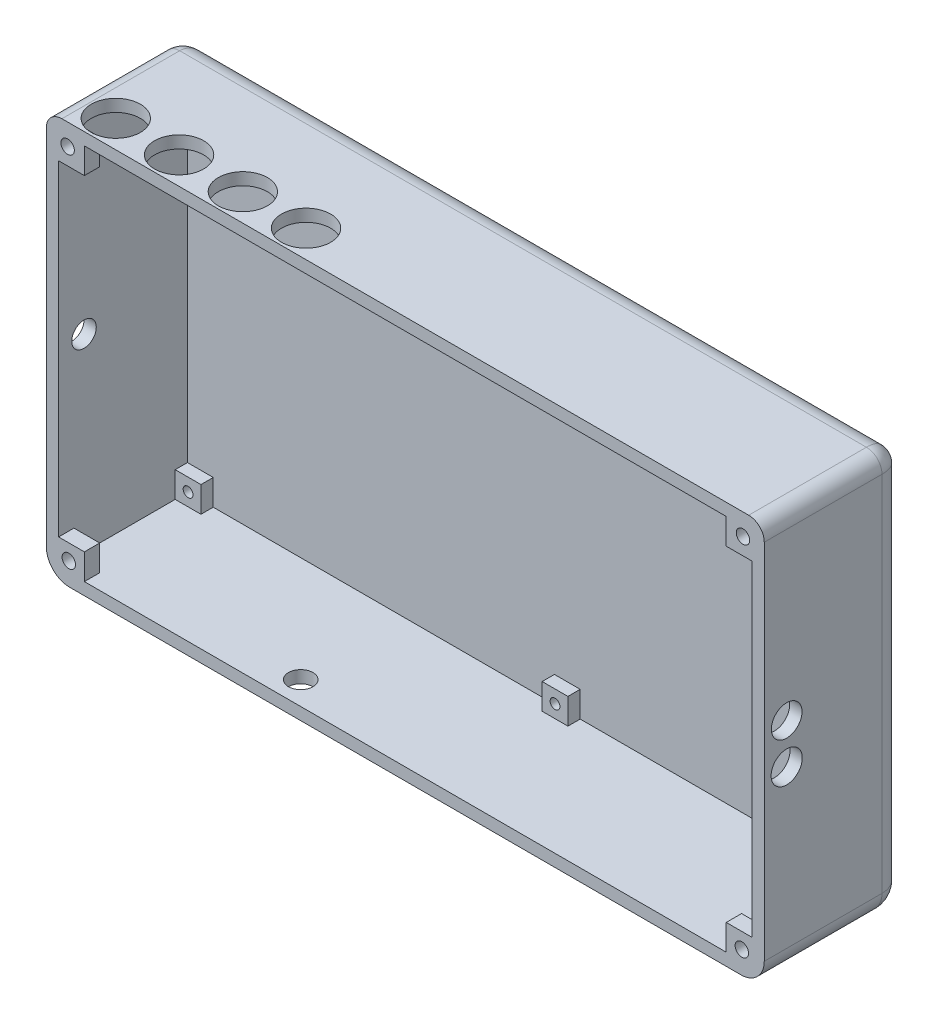
SolidWorks part; units mm, degrees
ref_plane "Front Plane" through (0, 0, 0) normal (0, 0, 1) x (1, 0, 0)
ref_plane "Top Plane" through (0, 0, 0) normal (0, 1, 0) x (1, 0, 0)
ref_plane "Right Plane" through (0, 0, 0) normal (1, 0, 0) x (0, 0, -1)
sketch "Sketch1" plane through (0, 0, 0) normal (0, 0, 1) x (1, 0, 0)
  line L1 (58.5, -32.75) -> (-58.5, -32.75)
  line L2 (58.5, -32.75) -> (58.5, 32.75)
  line L3 (58.5, 32.75) -> (-58.5, 32.75)
  line L4 (-58.5, -32.75) -> (-58.5, 32.75)
  line L5 (0, 32.75) -> (0, -32.75) construction
  line L6 (58.5, 0) -> (-58.5, 0) construction
  point P0 (0, 0)
  dimension "D1" = 117
  dimension "D2" = 65.5
extrude "Boss-Extrude1" add sketch "Sketch1" along normal blind 23
sketch "Sketch2" plane through (0, 0, 23) normal (0, 0, 1) x (1, 0, 0)
  line L1 (56.5, -30.75) -> (-56.5, -30.75)
  line L2 (56.5, -30.75) -> (56.5, 30.75)
  line L3 (56.5, 30.75) -> (-56.5, 30.75)
  line L4 (-56.5, -30.75) -> (-56.5, 30.75)
  line L5 (0, 30.75) -> (0, -30.75) construction
  line L6 (56.5, 0) -> (-56.5, 0) construction
  point P1 (0, 0)
  dimension "D1" = 113
  dimension "D2" = 61.5
extrude "Cut-Extrude1" cut sketch "Sketch2" against normal blind 21
sketch "Sketch3" plane through (0, 0, 2) normal (0, 0, 1) x (1, 0, 0)
  line L1 (-56.5, 30.75) -> (-52.3, 30.75)
  line L2 (-56.5, 30.75) -> (-56.5, 26.55)
  line L3 (-56.5, 26.55) -> (-52.3, 26.55)
  line L4 (-52.3, 30.75) -> (-52.3, 26.55)
  dimension "D1" = 4.2
  dimension "D2" = 4.2
extrude "Boss-Extrude3" add sketch "Sketch3" along normal blind 2
sketch "Sketch5" plane through (0, 0, 2) normal (0, 0, 1) x (1, 0, 0)
  line L0 (-56.5, -30.75) -> (7.5, -30.75) construction
  line L1 (-56.5, -30.75) -> (56.5, -30.75) construction
  line L3 (-56.5, -30.75) -> (-52.3, -30.75)
  line L4 (-56.5, -30.75) -> (-56.5, -26.55)
  line L5 (-56.5, -26.55) -> (-52.3, -26.55)
  line L6 (-52.3, -30.75) -> (-52.3, -26.55)
  line L7 (7.5, -30.75) -> (3.3, -30.75)
  line L8 (7.5, -30.75) -> (7.5, -26.55)
  line L9 (7.5, -26.55) -> (3.3, -26.55)
  line L10 (3.3, -30.75) -> (3.3, -26.55)
  dimension "D1" = 64
  dimension "D2" = 4.2
  dimension "D3" = 4.2
  dimension "D4" = 4.2
  dimension "D5" = 4.2
extrude "Boss-Extrude4" add sketch "Sketch5" along normal blind 2
sketch "Sketch6" plane through (0, 0, 2) normal (0, 0, 1) x (1, 0, 0)
  line L0 (-56.5, 26.55) -> (7.5, 26.55) construction
  line L1 (7.5, -26.55) -> (7.5, 30.75) construction
  line L5 (7.5, 30.75) -> (3.3, 30.75)
  line L6 (7.5, 30.75) -> (7.5, 26.55)
  line L7 (7.5, 26.55) -> (3.3, 26.55)
  line L8 (3.3, 30.75) -> (3.3, 26.55)
  dimension "D1" = 64
  dimension "D2" = 4.2
  dimension "D3" = 4.2
extrude "Boss-Extrude5" add sketch "Sketch6" along normal blind 2
sketch "Sketch7" plane through (0, 0, 4) normal (0, 0, 1) x (1, 0, 0)
  line L0 (-56.5, 30.75) -> (-52.3, 26.55) construction
  line L1 (-52.3, 26.55) -> (-52.3, 30.75) construction
  line L2 (-52.3, 26.55) -> (-52.3, 30.75) construction
  line L3 (-52.3, 30.75) -> (-56.5, 26.55) construction
  line L4 (-56.5, 26.55) -> (7.5, 30.75) construction
  line L5 (7.5, 30.75) -> (3.3, 26.55) construction
  line L6 (3.3, 26.55) -> (7.5, 26.55) construction
  line L7 (7.5, 26.55) -> (3.3, 30.75) construction
  line L8 (3.3, 30.75) -> (7.5, -30.75) construction
  line L9 (7.5, -30.75) -> (3.3, -26.55) construction
  line L10 (7.5, -26.55) -> (3.3, -26.55) construction
  line L11 (3.3, -26.55) -> (7.5, -26.55) construction
  line L12 (7.5, -26.55) -> (3.3, -30.75) construction
  line L13 (3.3, -30.75) -> (-56.5, -30.75) construction
  line L14 (-56.5, -30.75) -> (-52.3, -26.55) construction
  line L15 (-52.3, -26.55) -> (-52.3, -30.75) construction
  line L16 (-52.3, -30.75) -> (-56.5, -26.55) construction
  circle A0 centre (-54.4, -28.65) radius 0.8
  dimension "D1" = 1.6
extrude "Cut-Extrude2" cut sketch "Sketch7" against normal blind 2
sketch "Sketch8" plane through (0, 0, 4) normal (0, 0, 1) x (1, 0, 0)
  line L0 (3.3, -26.55) -> (3.6877, -26.9377) construction
  line L1 (7.5, -30.75) -> (3.3, -26.55) construction
  line L2 (3.3, -26.55) -> (7.5, -26.55) construction
  line L3 (7.5, -26.55) -> (3.3, -30.75) construction
  circle A0 centre (5.4, -28.65) radius 0.8
  dimension "D1" = 1.6
extrude "Cut-Extrude3" cut sketch "Sketch8" against normal blind 2
sketch "Sketch9" plane through (0, 0, 4) normal (0, 0, 1) x (1, 0, 0)
  line L0 (3.3, 30.75) -> (7.5, 26.55) construction
  line L1 (7.5, 26.55) -> (7.5, 30.75) construction
  line L2 (7.5, 30.75) -> (3.3, 26.55) construction
  circle A0 centre (5.4, 28.65) radius 0.8
  dimension "D1" = 1.6
extrude "Cut-Extrude4" cut sketch "Sketch9" against normal blind 2
sketch "Sketch10" plane through (0, 0, 4) normal (0, 0, 1) x (1, 0, 0)
  line L0 (-56.5, 30.75) -> (-52.3, 26.55) construction
  line L1 (-52.3, 26.55) -> (-52.3, 30.75) construction
  line L2 (-52.3, 30.75) -> (-56.5, 26.55) construction
  circle A0 centre (-54.4, 28.65) radius 0.8
  dimension "D1" = 1.6
extrude "Cut-Extrude6" cut sketch "Sketch10" against normal blind 2
sketch "Sketch11" plane through (0, 30.75, 0) normal (0, -1, 0) x (-1, 0, 0)
  line L0 (56.5, -23) -> (56.5, -14.11) construction
  line L1 (56.5, -4) -> (56.5, -23) construction
  line L4 (47.6269, -18.555) -> (41.3092, -18.555) construction
  line L5 (37.3092, -18.555) -> (30.9182, -18.555) construction
  line L6 (26.9182, -18.555) -> (20.6182, -18.555) construction
  circle A0 centre (51.6269, -18.555) radius 4
  circle A1 centre (41.3092, -18.555) radius 4
  circle A2 centre (30.9182, -18.555) radius 4
  circle A3 centre (20.6182, -18.555) radius 4
  point P10 (56.5, -18.555)
  dimension "D2" = 8
  dimension "D3" = 8
  dimension "D4" = 8
  dimension "D5" = 8
  dimension "D1" = 8.89
extrude "Cut-Extrude7" cut sketch "Sketch11" against normal through all
sketch "Sketch12" plane through (-56.5, 0, 0) normal (1, 0, 0) x (0, 0, -1)
  line L0 (-23, 30.75) -> (-23, -30.75) construction
  line L1 (-23, -30.75) -> (-23, 0) construction
  line L2 (-23, 0) -> (-2, 0) construction
  line L3 (-2, 26.55) -> (-2, -26.55) construction
  line L4 (-23, 0) -> (-19.478, 0) construction
  line L5 (-23, 0) -> (-18.8595, 0) construction
  circle A0 centre (-18.8595, 0) radius 2
  dimension "D1" = 4
extrude "Cut-Extrude8" cut sketch "Sketch12" against normal through all
sketch "Sketch14" plane through (0, -30.75, 0) normal (0, 1, 0) x (1, 0, 0)
  line L0 (-52.3, -4) -> (-52.3, -23) construction
  line L1 (-56.5, -23) -> (56.5, -23) construction
  line L2 (-52.3, -23) -> (3.3, -4) construction
  line L3 (3.3, -4) -> (9.7928, -23) construction
  line L4 (9.7928, -23) -> (-52.3, -4) construction
  line L5 (-22.9663, -12.9759) -> (-18.7088, -25.435) construction
  circle A0 centre (-20.8375, -19.2054) radius 2
  dimension "D1" = 4
extrude "Cut-Extrude11" cut sketch "Sketch14" against normal through all
sketch "Sketch17" plane through (56.5, 0, 0) normal (-1, 0, 0) x (0, 0, 1)
  line L0 (23, 30.75) -> (2, -30.75) construction
  line L1 (2, -30.75) -> (23, -30.75) construction
  line L2 (23, -30.75) -> (2, 30.75) construction
  line L3 (12.5, 0) -> (23, 0) construction
  line L4 (23, -30.75) -> (23, 30.75) construction
  line L5 (23, 30.75) -> (19.3482, 28.9611) construction
  line L6 (19.3482, 28.9611) -> (19.3482, -30.75) construction
  line L7 (19.3482, 3.2358) -> (19.3482, -3.3223) construction
  circle A0 centre (19.3482, 3.2358) radius 2.5
  circle A1 centre (19.3482, -3.3223) radius 2.54
  dimension "D1" = 5
  dimension "D2" = 5.08
  dimension "D3" = 5
extrude "Cut-Extrude18" cut sketch "Sketch17" against normal through all
fillet "Fillet1" radius 2.54 1 edges at (-58.5, 32.75, 11.5)
fillet "Fillet2" radius 2.54 1 edges at (58.5, 32.75, 11.5)
fillet "Fillet3" radius 3.81 1 edges at (-58.5, -32.75, 11.5)
fillet "Fillet4" radius 3.81 1 edges at (58.5, -32.75, 11.5)
fillet "Fillet8" radius 3.81 8 edges at (57.7561, 32.0061, 0) (0, 32.75, 0) (-57.7561, 32.0061, 0) (-58.5, 0.635, 0) (-57.3841, -31.6341, 0) (0, -32.75, 0) (57.3841, -31.6341, 0) (58.5, 0.635, 0)
sketch "Sketch18" plane through (0, 0, 23) normal (0, 0, 1) x (1, 0, 0)
  line L1 (-56.5, 30.75) -> (-52.3, 30.75)
  line L2 (-56.5, 30.75) -> (-56.5, 26.55)
  line L3 (-56.5, 26.55) -> (-52.3, 26.55)
  line L4 (-52.3, 30.75) -> (-52.3, 26.55)
  dimension "D1" = 4.2
  dimension "D2" = 4.2
extrude "Boss-Extrude6" add sketch "Sketch18" against normal blind 2.5
sketch "Sketch19" plane through (0, 0, 23) normal (0, 0, 1) x (1, 0, 0)
  line L1 (-56.5, -30.75) -> (-52.3, -30.75)
  line L2 (-56.5, -30.75) -> (-56.5, -26.55)
  line L3 (-56.5, -26.55) -> (-52.3, -26.55)
  line L4 (-52.3, -30.75) -> (-52.3, -26.55)
  dimension "D1" = 4.2
  dimension "D2" = 4.2
extrude "Boss-Extrude7" add sketch "Sketch19" against normal blind 2.5
sketch "Sketch21" plane through (0, 0, 23) normal (0, 0, 1) x (1, 0, 0)
  line L1 (56.5, 30.75) -> (52.3, 30.75)
  line L2 (56.5, 30.75) -> (56.5, 26.55)
  line L3 (56.5, 26.55) -> (52.3, 26.55)
  line L4 (52.3, 30.75) -> (52.3, 26.55)
  dimension "D1" = 4.2
  dimension "D2" = 4.2
extrude "Boss-Extrude8" add sketch "Sketch21" against normal blind 2.5
sketch "Sketch22" plane through (0, 0, 23) normal (0, 0, 1) x (1, 0, 0)
  line L1 (56.5, -30.75) -> (52.3, -30.75)
  line L2 (56.5, -30.75) -> (56.5, -26.55)
  line L3 (56.5, -26.55) -> (52.3, -26.55)
  line L4 (52.3, -30.75) -> (52.3, -26.55)
  dimension "D1" = 4.2
  dimension "D2" = 4.2
extrude "Boss-Extrude9" add sketch "Sketch22" against normal blind 2.5
sketch "Sketch23" plane through (0, 0, 23) normal (0, 0, 1) x (1, 0, 0)
  line L0 (-52.3, 30.75) -> (-56.5, 26.55) construction
  line L1 (-56.5, 26.55) -> (-52.3, 26.55) construction
  line L2 (-52.3, 26.55) -> (-57.7561, 32.0061) construction
  arc A0 (-55.96, 32.75) -> (-58.5, 30.21) centre (-55.96, 30.21) ccw construction
  circle A1 centre (-55.028, 29.278) radius 1.0922
  dimension "D1" = 2.1844
extrude "Cut-Extrude19" cut sketch "Sketch23" against normal blind 2
sketch "Sketch24" plane through (0, 0, 23) normal (0, 0, 1) x (1, 0, 0)
  line L0 (52.3, 26.55) -> (57.7561, 32.0061) construction
  line L1 (57.7561, 32.0061) -> (52.3, 30.75) construction
  line L2 (52.3, 30.75) -> (56.5, 26.55) construction
  arc A0 (58.5, 30.21) -> (55.96, 32.75) centre (55.96, 30.21) ccw construction
  circle A1 centre (55.028, 29.278) radius 1.0922
  dimension "D1" = 2.1844
extrude "Cut-Extrude20" cut sketch "Sketch24" against normal blind 2
sketch "Sketch25" plane through (0, 0, 23) normal (0, 0, 1) x (1, 0, 0)
  line L0 (52.3, -26.55) -> (57.3841, -31.6341) construction
  line L1 (57.3841, -31.6341) -> (56.5, -26.55) construction
  line L2 (56.5, -26.55) -> (52.3, -30.75) construction
  arc A0 (54.69, -32.75) -> (58.5, -28.94) centre (54.69, -28.94) ccw construction
  circle A1 centre (54.842, -29.092) radius 1.0922
  dimension "D1" = 2.1844
extrude "Cut-Extrude21" cut sketch "Sketch25" against normal blind 2
sketch "Sketch26" plane through (0, 0, 23) normal (0, 0, 1) x (1, 0, 0)
  line L0 (-52.3, -26.55) -> (-57.3841, -31.6341) construction
  line L1 (-57.3841, -31.6341) -> (-56.5, -26.55) construction
  line L2 (-56.5, -26.55) -> (-52.3, -30.75) construction
  arc A0 (-58.5, -28.94) -> (-54.69, -32.75) centre (-54.69, -28.94) ccw construction
  circle A1 centre (-54.842, -29.092) radius 1.0922
  dimension "D1" = 2.1844
extrude "Cut-Extrude22" cut sketch "Sketch26" against normal blind 2
